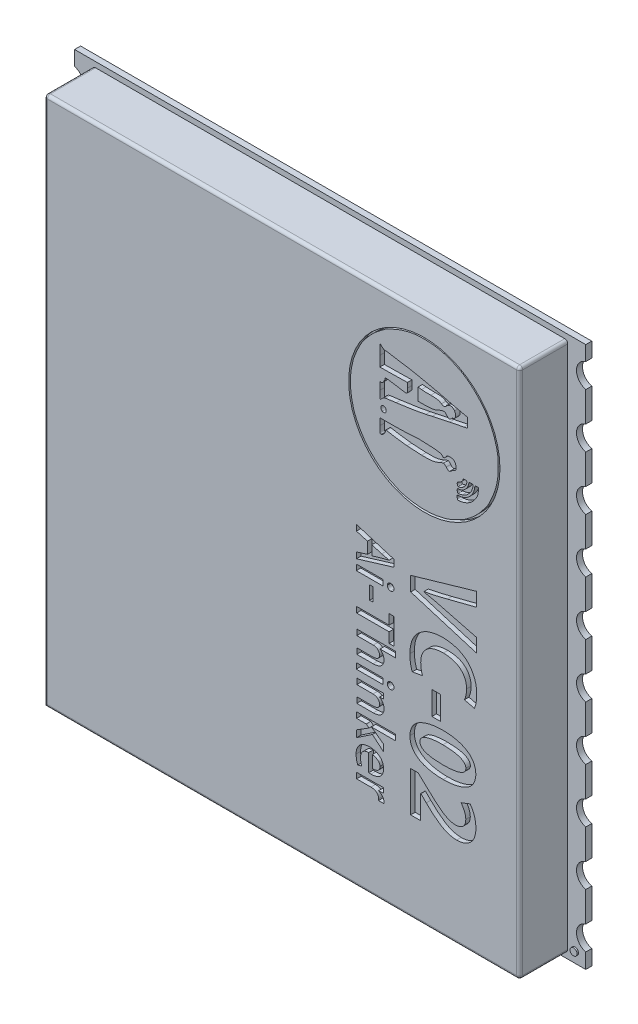
SolidWorks part; units mm, degrees
material "Alliage 1060"
ref_plane "Plan de face" through (0, 0, 0) normal (0, 0, 1) x (1, 0, 0)
ref_plane "Plan de dessus" through (0, 0, 0) normal (0, 1, 0) x (1, 0, 0)
ref_plane "Plan de droite" through (0, 0, 0) normal (1, 0, 0) x (0, 0, -1)
sketch "Esquisse1" plane through (0, 0, 0) normal (0, 0, 1) x (1, 0, 0)
  line L0 (-8.5, 9) -> (-8.5, 8.51) construction
  line L1 (-8.5, -9) -> (8.5, -9)
  line L2 (-8.5, -9) -> (-8.5, -8.4958)
  line L3 (-8.5, 9) -> (8.5, 9)
  line L4 (8.5, -9) -> (8.5, -8.4958)
  line L5 (-8.5, -9) -> (8.5, 9) construction
  line L6 (-8.5, 9) -> (8.5, -9) construction
  line L7 (-8.1924, 8.1048) -> (-8.0028, 8.1048) construction
  line L8 (-8.0028, 8.1048) -> (-8.0028, 8.6053) construction
  line L9 (-8.0028, 8.1048) -> (-8.0028, 7.6017) construction
  line L10 (-8.5, 8.6053) -> (-8.5, 8.51) construction
  line L11 (-8.5, 7.6044) -> (-8.0028, 7.6044)
  line L13 (-8.5, 8.6053) -> (-8.0028, 8.6053)
  line L14 (-8.0028, 7.6044) -> (-8.0028, 8.6053)
  line L15 (-8.2646, 8.3418) -> (-8.0028, 8.6053) construction
  line L16 (-8.2664, 7.8697) -> (-8.0028, 7.6044) construction
  line L17 (-8.5, 7.6044) -> (-8.5, 7.7042) construction
  line L18 (-8.5, 8.51) -> (-8.5, 9)
  line L19 (0, 9) -> (0, -9) construction
  line L20 (8.5, 7.6044) -> (8.0028, 7.6044)
  line L21 (8.0028, 7.6044) -> (8.0028, 8.6053)
  line L22 (8.5, 8.6053) -> (8.0028, 8.6053)
  line L23 (-8.5, 6.8053) -> (-8.0028, 6.8053)
  line L24 (-8.0028, 5.8044) -> (-8.0028, 6.8053)
  line L25 (-8.5, 5.8044) -> (-8.0028, 5.8044)
  line L26 (8.0028, 5.8044) -> (8.0028, 6.8053)
  line L27 (8.5, 6.8053) -> (8.0028, 6.8053)
  line L28 (8.5, 5.8044) -> (8.0028, 5.8044)
  line L29 (-8.5, 5.0053) -> (-8.0028, 5.0053)
  line L30 (-8.0028, 4.0044) -> (-8.0028, 5.0053)
  line L31 (-8.5, 4.0044) -> (-8.0028, 4.0044)
  line L32 (8.0028, 4.0044) -> (8.0028, 5.0053)
  line L33 (8.5, 5.0053) -> (8.0028, 5.0053)
  line L34 (8.5, 4.0044) -> (8.0028, 4.0044)
  line L35 (-8.5, 3.2053) -> (-8.0028, 3.2053)
  line L36 (-8.0028, 2.2044) -> (-8.0028, 3.2053)
  line L37 (-8.5, 2.2044) -> (-8.0028, 2.2044)
  line L38 (8.0028, 2.2044) -> (8.0028, 3.2053)
  line L39 (8.5, 3.2053) -> (8.0028, 3.2053)
  line L40 (8.5, 2.2044) -> (8.0028, 2.2044)
  line L41 (-8.5, 1.4053) -> (-8.0028, 1.4053)
  line L42 (-8.0028, 0.4044) -> (-8.0028, 1.4053)
  line L43 (-8.5, 0.4044) -> (-8.0028, 0.4044)
  line L44 (8.0028, 0.4044) -> (8.0028, 1.4053)
  line L45 (8.5, 1.4053) -> (8.0028, 1.4053)
  line L46 (8.5, 0.4044) -> (8.0028, 0.4044)
  line L47 (-8.5, -0.3947) -> (-8.0028, -0.3947)
  line L48 (-8.0028, -1.3956) -> (-8.0028, -0.3947)
  line L49 (-8.5, -1.3956) -> (-8.0028, -1.3956)
  line L50 (8.0028, -1.3956) -> (8.0028, -0.3947)
  line L51 (8.5, -0.3947) -> (8.0028, -0.3947)
  line L52 (8.5, -1.3956) -> (8.0028, -1.3956)
  line L53 (-8.5, -2.1947) -> (-8.0028, -2.1947)
  line L54 (-8.0028, -3.1956) -> (-8.0028, -2.1947)
  line L55 (-8.5, -3.1956) -> (-8.0028, -3.1956)
  line L56 (8.0028, -3.1956) -> (8.0028, -2.1947)
  line L57 (8.5, -2.1947) -> (8.0028, -2.1947)
  line L58 (8.5, -3.1956) -> (8.0028, -3.1956)
  line L59 (-8.5, -3.9947) -> (-8.0028, -3.9947)
  line L60 (-8.0028, -4.9956) -> (-8.0028, -3.9947)
  line L61 (-8.5, -4.9956) -> (-8.0028, -4.9956)
  line L62 (8.0028, -4.9956) -> (8.0028, -3.9947)
  line L63 (8.5, -3.9947) -> (8.0028, -3.9947)
  line L64 (8.5, -4.9956) -> (8.0028, -4.9956)
  line L65 (-8.5, -5.7947) -> (-8.0028, -5.7947)
  line L66 (-8.0028, -6.7956) -> (-8.0028, -5.7947)
  line L67 (-8.5, -6.7956) -> (-8.0028, -6.7956)
  line L68 (8.0028, -6.7956) -> (8.0028, -5.7947)
  line L69 (8.5, -5.7947) -> (8.0028, -5.7947)
  line L70 (8.5, -6.7956) -> (8.0028, -6.7956)
  line L71 (-8.5, -7.5947) -> (-8.0028, -7.5947)
  line L72 (-8.0028, -8.5956) -> (-8.0028, -7.5947)
  line L73 (-8.5, -8.5956) -> (-8.0028, -8.5956)
  line L74 (8.0028, -8.5956) -> (8.0028, -7.5947)
  line L75 (8.5, -7.5947) -> (8.0028, -7.5947)
  line L76 (8.5, -8.5956) -> (8.0028, -8.5956)
  line L77 (-8.5, 6.71) -> (-8.5, 7.7042)
  line L78 (-8.5, 4.91) -> (-8.5, 5.9042)
  line L79 (-8.5, 3.11) -> (-8.5, 4.1042)
  line L80 (-8.5, 1.31) -> (-8.5, 2.3042)
  line L81 (-8.5, -0.49) -> (-8.5, 0.5042)
  line L82 (-8.5, -2.29) -> (-8.5, -1.2958)
  line L83 (-8.5, -4.09) -> (-8.5, -3.0958)
  line L84 (-8.5, -5.89) -> (-8.5, -4.8958)
  line L85 (-8.5, -7.69) -> (-8.5, -6.6958)
  line L86 (8.5, 8.51) -> (8.5, 9)
  line L87 (8.5, 6.71) -> (8.5, 7.7042)
  line L88 (8.5, 3.11) -> (8.5, 5.9042)
  line L89 (8.5, -0.49) -> (8.5, 2.3042)
  line L90 (8.5, -2.29) -> (8.5, -1.2958)
  line L91 (8.5, -4.09) -> (8.5, -3.0958)
  line L92 (8.5, -5.89) -> (8.5, -4.8958)
  line L93 (8.5, -7.69) -> (8.5, -6.6958)
  arc A0 (-8.5, 8.51) -> (-8.5, 7.7042) centre (-8.61, 8.1071) cw
  arc A1 (8.5, 8.51) -> (8.5, 7.7042) centre (8.61, 8.1071) ccw
  arc A2 (-8.5, 6.71) -> (-8.5, 5.9042) centre (-8.61, 6.3071) cw
  arc A3 (8.5, 6.71) -> (8.5, 5.9042) centre (8.61, 6.3071) ccw
  arc A4 (-8.5, 4.91) -> (-8.5, 4.1042) centre (-8.61, 4.5071) cw
  arc A5 (8.5, 4.91) -> (8.5, 4.1042) centre (8.61, 4.5071) ccw
  arc A6 (-8.5, 3.11) -> (-8.5, 2.3042) centre (-8.61, 2.7071) cw
  arc A7 (8.5, 3.11) -> (8.5, 2.3042) centre (8.61, 2.7071) ccw
  arc A8 (-8.5, 1.31) -> (-8.5, 0.5042) centre (-8.61, 0.9071) cw
  arc A9 (8.5, 1.31) -> (8.5, 0.5042) centre (8.61, 0.9071) ccw
  arc A10 (-8.5, -0.49) -> (-8.5, -1.2958) centre (-8.61, -0.8929) cw
  arc A11 (8.5, -0.49) -> (8.5, -1.2958) centre (8.61, -0.8929) ccw
  arc A12 (-8.5, -2.29) -> (-8.5, -3.0958) centre (-8.61, -2.6929) cw
  arc A13 (8.5, -2.29) -> (8.5, -3.0958) centre (8.61, -2.6929) ccw
  arc A14 (-8.5, -4.09) -> (-8.5, -4.8958) centre (-8.61, -4.4929) cw
  arc A15 (8.5, -4.09) -> (8.5, -4.8958) centre (8.61, -4.4929) ccw
  arc A16 (-8.5, -5.89) -> (-8.5, -6.6958) centre (-8.61, -6.2929) cw
  arc A17 (8.5, -5.89) -> (8.5, -6.6958) centre (8.61, -6.2929) ccw
  arc A18 (-8.5, -7.69) -> (-8.5, -8.4958) centre (-8.61, -8.0929) cw
  arc A19 (8.5, -7.69) -> (8.5, -8.4958) centre (8.61, -8.0929) ccw
  point P0 (0, 0)
  dimension "D1" = 17
  dimension "D2" = 18
  dimension "D3" = 10
extrude "Boss.-Extru.1" add sketch "Esquisse1" along normal blind 0.2 contours L75 L93 L70 L68 L69 L92 L64 L62 L63 L91 L58 L56 L57 L90 L52 L50 L51 L89 L46 L44 L45 L40 L38 L39 L88 L34 L32 L33 L28 L26 L27 L87 L20 L21 L22 L86 L3 L18 L13 L14 L11 L77 L23 L24 L25 L78 L29 L30 L31 | L18 A0 L77 L11 L14 L13 | L77 A2 L78 L25 L24 L23 | L78 A4 L79 L31 L30 L29 | L79 A6 L80 L37 L36 L35 | L80 A8 L81 L43 L42 L41 | L81 A10 L82 L49 L48 L47 | L82 A12 L83 L55 L54 L53 | L83 A14 L84 L61 L60 L59 | L84 A16 L85 L67 L66 L65 | L85 A18 L2 L73 L72 L71 | A1 L86 L22 L21 L20 L87 | A3 L87 L27 L26 L28 L88 | A5 L88 L33 L32 L34 | A7 L88 L39 L38 L40 L89 | A9 L89 L45 L44 L46 | A11 L89 L51 L50 L52 L90 | A13 L90 L57 L56 L58 L91 | A15 L91 L63 L62 L64 L92 | A17 L92 L69 L68 L70 L93 | A19 L93 L75 L74 L76 L4 region at (0, -0.0002, 0) region at (-8.1811, -8.0965, 0) region at (8.1811, -8.0965, 0) region at (-8.1811, -6.2965, 0) region at (8.1811, -6.2965, 0) region at (-8.1811, -4.4965, 0) region at (8.1811, -4.4965, 0) region at (-8.1811, -2.6965, 0) region at (8.1811, -2.6965, 0) region at (-8.1811, -0.8965, 0) region at (8.1811, -0.8965, 0) region at (-8.1811, 0.9035, 0) region at (8.1811, 0.9035, 0) region at (-8.1811, 2.7035, 0) region at (8.1811, 2.7035, 0) region at (-8.1811, 4.5035, 0) region at (8.1811, 4.5035, 0) region at (-8.1811, 6.3035, 0) region at (8.1811, 6.3035, 0) region at (-8.1811, 8.1035, 0) region at (8.1811, 8.1035, 0)
sketch "Esquisse2" plane through (0, 0, 0.2) normal (0, 0, 1) x (1, 0, 0)
  line L1 (-7.9016, -8.8212) -> (7.9016, -8.8212)
  line L2 (-7.9016, -8.8212) -> (-7.9016, 8.8212)
  line L3 (-7.9016, 8.8212) -> (7.9016, 8.8212)
  line L4 (7.9016, -8.8212) -> (7.9016, 8.8212)
  line L5 (-7.9016, -8.8212) -> (7.9016, 8.8212) construction
  line L6 (-7.9016, 8.8212) -> (7.9016, -8.8212) construction
  point P0 (0, 0)
extrude "Boss.-Extru.2" add sketch "Esquisse2" along normal blind 1.6
fillet "Congé1" radius 0.1 7 edges at (7.9016, -8.8212, 1) (-7.9016, 8.8212, 1) (7.9016, 8.8212, 1) (0, 8.8212, 1.8) (7.9016, 0, 1.8) (0, -8.8212, 1.8) (-7.9016, 0, 1.8)
sketch "Esquisse3" plane through (0, 0, 0.2) normal (0, 0, 1) x (1, 0, 0)
  circle A0 centre (8.1429, -8.6444) radius 0.1165
extrude "Boss.-Extru.3" add sketch "Esquisse3" along normal blind 0.05
sketch "Esquisse4" plane through (4.0778, 3.5696, 1.8) normal (0, 0, 1) x (0, -1, 0)
  line L0 (-2.9667, -0.368) -> (-2.9744, 0.0906)
  line L1 (-2.9744, 0.0906) -> (-2.8102, 0.0906)
  line L2 (-2.5452, -0.7857) -> (-2.553, -0.8265)
  line L3 (-2.553, -0.8265) -> (-2.2899, -0.8265)
  line L4 (-2.6311, 1.9732) -> (-2.6513, 2.0834)
  line L5 (-2.6513, 2.0834) -> (-2.8119, 2.0834)
  line L6 (-2.8119, 2.0834) -> (-2.9724, 2.0834)
  line L7 (-2.9724, 2.0834) -> (-3.0142, 1.8938)
  line L8 (-3.2964, -0.8265) -> (-2.9591, -0.8265)
  line L9 (-2.9591, -0.8265) -> (-2.9667, -0.368)
  line L10 (-2.6108, 0.6535) -> (-2.6108, 0.4433)
  line L11 (-2.6108, 0.4433) -> (-2.8151, 0.4433)
  line L12 (-2.8151, 0.4433) -> (-3.0193, 0.4433)
  line L13 (-3.0193, 0.4433) -> (-3.0053, 0.5623)
  line L14 (-1.5006, -0.4076) -> (-1.4998, -0.8265)
  line L15 (-1.4998, -0.8265) -> (-1.2705, -0.8265)
  line L16 (-1.0074, 2.4486) -> (-1.1295, 2.4588)
  line L17 (-1.1295, 2.4588) -> (-1.1295, 2.397)
  line L18 (-0.5699, 1.8409) -> (-0.5602, 1.7483)
  line L19 (-0.5602, 1.7483) -> (-0.4921, 1.7483)
  line L20 (-2.0465, 3.1105) -> (-2.0192, -1.8037) construction
  line L21 (-4.5021, 0.6549) -> (0.4101, 0.7018) construction
  circle A0 centre (-2.0329, 0.6534) radius 2.516
  spline S0 degree 3 poles (-2.267, -1.795) (-2.4108, -1.7826) (-2.4888, -1.7682) (-2.7343, -1.7088) knots 0 0 0 0 1 1 1 1
  spline S1 degree 3 poles (-2.7343, -1.7088) (-2.8848, -1.6724) (-3.28, -1.4898) (-3.3951, -1.4036) knots 0 0 0 0 1 1 1 1
  spline S2 degree 3 poles (-3.3951, -1.4036) (-3.4239, -1.382) (-3.4993, -1.3255) (-3.5626, -1.2781) knots 0 0 0 0 1 1 1 1
  spline S3 degree 3 poles (-3.5626, -1.2781) (-3.7172, -1.1624) (-3.8836, -0.9907) (-4.0177, -0.8088) knots 0 0 0 0 1 1 1 1
  spline S4 degree 3 poles (-4.0177, -0.8088) (-4.0784, -0.7264) (-4.1353, -0.6501) (-4.1439, -0.6393) knots 0 0 0 0 1 1 1 1
  spline S5 degree 3 poles (-4.1439, -0.6393) (-4.1756, -0.5998) (-4.3364, -0.2503) (-4.3702, -0.1475) knots 0 0 0 0 1 1 1 1
  spline S6 degree 3 poles (-4.3702, -0.1475) (-4.477, 0.1775) (-4.5021, 0.3305) (-4.5021, 0.6549) knots 0 0 0 0 1 1 1 1
  spline S7 degree 3 poles (-4.5021, 0.6549) (-4.5021, 0.9793) (-4.477, 1.1323) (-4.3702, 1.4573) knots 0 0 0 0 1 1 1 1
  spline S8 degree 3 poles (-4.3702, 1.4573) (-4.3286, 1.5839) (-4.169, 1.9209) (-4.1343, 1.9557) knots 0 0 0 0 1 1 1 1
  spline S9 degree 3 poles (-4.1343, 1.9557) (-4.1207, 1.9692) (-4.1005, 1.9975) (-4.0894, 2.0186) knots 0 0 0 0 1 1 1 1
  spline S10 degree 3 poles (-4.0894, 2.0186) (-3.9946, 2.1985) (-3.5901, 2.603) (-3.4102, 2.6978) knots 0 0 0 0 1 1 1 1
  spline S11 degree 3 poles (-3.4102, 2.6978) (-3.3892, 2.7089) (-3.3608, 2.7291) (-3.3473, 2.7427) knots 0 0 0 0 1 1 1 1
  spline S12 degree 3 poles (-3.3473, 2.7427) (-3.3125, 2.7774) (-2.9755, 2.937) (-2.8489, 2.9786) knots 0 0 0 0 1 1 1 1
  spline S13 degree 3 poles (-2.8489, 2.9786) (-2.5239, 3.0854) (-2.3709, 3.1105) (-2.0465, 3.1105) knots 0 0 0 0 1 1 1 1
  spline S14 degree 3 poles (-2.0465, 3.1105) (-1.7221, 3.1105) (-1.5691, 3.0854) (-1.2441, 2.9786) knots 0 0 0 0 1 1 1 1
  spline S15 degree 3 poles (-1.2441, 2.9786) (-1.1413, 2.9448) (-0.7918, 2.784) (-0.7523, 2.7523) knots 0 0 0 0 1 1 1 1
  spline S16 degree 3 poles (-0.7523, 2.7523) (-0.7415, 2.7436) (-0.6652, 2.6868) (-0.5828, 2.6261) knots 0 0 0 0 1 1 1 1
  spline S17 degree 3 poles (-0.5828, 2.6261) (-0.4009, 2.492) (-0.2292, 2.3255) (-0.1135, 2.171) knots 0 0 0 0 1 1 1 1
  spline S18 degree 3 poles (-0.1135, 2.171) (-0.0661, 2.1077) (-0.0096, 2.0323) (0.012, 2.0035) knots 0 0 0 0 1 1 1 1
  spline S19 degree 3 poles (0.012, 2.0035) (0.0982, 1.8883) (0.2807, 1.4932) (0.3172, 1.3427) knots 0 0 0 0 1 1 1 1
  spline S20 degree 3 poles (0.3172, 1.3427) (0.375, 1.1039) (0.3902, 1.0167) (0.404, 0.8445) knots 0 0 0 0 1 1 1 1
  spline S21 degree 3 poles (0.404, 0.8445) (0.4302, 0.5163) (0.371, 0.064) (0.2695, -0.1828) knots 0 0 0 0 1 1 1 1
  spline S22 degree 3 poles (0.2695, -0.1828) (0.0616, -0.6881) (-0.2009, -1.0347) (-0.6004, -1.3318) knots 0 0 0 0 1 1 1 1
  spline S23 degree 3 poles (-0.6004, -1.3318) (-0.7952, -1.4766) (-1.173, -1.6679) (-1.326, -1.6991) knots 0 0 0 0 1 1 1 1
  spline S24 degree 3 poles (-1.326, -1.6991) (-1.3586, -1.7057) (-1.409, -1.7181) (-1.4381, -1.7265) knots 0 0 0 0 1 1 1 1
  spline S25 degree 3 poles (-1.4381, -1.7265) (-1.6677, -1.7931) (-1.9844, -1.8193) (-2.267, -1.795) knots 0 0 0 0 1 1 1 1
  spline S26 degree 3 poles (-2.8102, 0.0906) (-2.6221, 0.0906) (-2.6304, 0.1011) (-2.665, -0.0946) knots 0 0 0 0 1 1 1 1
  spline S27 degree 3 poles (-2.665, -0.0946) (-2.6753, -0.1528) (-2.6911, -0.252) (-2.7002, -0.3151) knots 0 0 0 0 1 1 1 1
  spline S28 degree 3 poles (-2.7002, -0.3151) (-2.7093, -0.3781) (-2.7236, -0.4733) (-2.7321, -0.5267) knots 0 0 0 0 1 1 1 1
  spline S29 degree 3 poles (-2.7321, -0.5267) (-2.7489, -0.6326) (-2.7453, -0.6501) (-2.7064, -0.6501) knots 0 0 0 0 1 1 1 1
  spline S30 degree 3 poles (-2.7064, -0.6501) (-2.6922, -0.6501) (-2.6484, -0.6714) (-2.609, -0.6975) knots 0 0 0 0 1 1 1 1
  spline S31 degree 3 poles (-2.609, -0.6975) (-2.5525, -0.7349) (-2.5391, -0.7534) (-2.5452, -0.7857) knots 0 0 0 0 1 1 1 1
  spline S32 degree 3 poles (-2.2899, -0.8265) (-2.0082, -0.8265) (-2.0041, -0.8247) (-2.1012, -0.7429) knots 0 0 0 0 1 1 1 1
  spline S33 degree 3 poles (-2.1012, -0.7429) (-2.132, -0.717) (-2.1517, -0.6798) (-2.1574, -0.6369) knots 0 0 0 0 1 1 1 1
  spline S34 degree 3 poles (-2.1574, -0.6369) (-2.1622, -0.6005) (-2.1833, -0.4398) (-2.2043, -0.2798) knots 0 0 0 0 1 1 1 1
  spline S35 degree 3 poles (-2.2043, -0.2798) (-2.2636, 0.1717) (-2.3254, 0.5547) (-2.3637, 0.7078) knots 0 0 0 0 1 1 1 1
  spline S36 degree 3 poles (-2.3637, 0.7078) (-2.3722, 0.7418) (-2.3923, 0.833) (-2.4084, 0.9106) knots 0 0 0 0 1 1 1 1
  spline S37 degree 3 poles (-2.4084, 0.9106) (-2.438, 1.0536) (-2.4838, 1.268) (-2.5326, 1.4926) knots 0 0 0 0 1 1 1 1
  spline S38 degree 3 poles (-2.5326, 1.4926) (-2.577, 1.6969) (-2.6098, 1.8568) (-2.6311, 1.9732) knots 0 0 0 0 1 1 1 1
  spline S39 degree 3 poles (-3.0142, 1.8938) (-3.0373, 1.7895) (-3.0626, 1.6804) (-3.0704, 1.6513) knots 0 0 0 0 1 1 1 1
  spline S40 degree 3 poles (-3.0704, 1.6513) (-3.114, 1.4904) (-3.1649, 1.2846) (-3.186, 1.184) knots 0 0 0 0 1 1 1 1
  spline S41 degree 3 poles (-3.186, 1.184) (-3.1992, 1.1209) (-3.2224, 1.0177) (-3.2376, 0.9547) knots 0 0 0 0 1 1 1 1
  spline S42 degree 3 poles (-3.2376, 0.9547) (-3.2527, 0.8917) (-3.2765, 0.7845) (-3.2903, 0.7166) knots 0 0 0 0 1 1 1 1
  spline S43 degree 3 poles (-3.2903, 0.7166) (-3.3042, 0.6487) (-3.3281, 0.5337) (-3.3435, 0.4609) knots 0 0 0 0 1 1 1 1
  spline S44 degree 3 poles (-3.3435, 0.4609) (-3.3917, 0.2334) (-3.406, 0.1513) (-3.459, -0.2004) knots 0 0 0 0 1 1 1 1
  spline S45 degree 3 poles (-3.459, -0.2004) (-3.478, -0.3265) (-3.5012, -0.468) (-3.5107, -0.5148) knots 0 0 0 0 1 1 1 1
  spline S46 degree 3 poles (-3.5107, -0.5148) (-3.5202, -0.5616) (-3.5279, -0.6239) (-3.5279, -0.6532) knots 0 0 0 0 1 1 1 1
  spline S47 degree 3 poles (-3.5279, -0.6532) (-3.5279, -0.6897) (-3.5446, -0.7221) (-3.5808, -0.7559) knots 0 0 0 0 1 1 1 1
  spline S48 degree 3 poles (-3.5808, -0.7559) (-3.6099, -0.7831) (-3.6337, -0.8101) (-3.6337, -0.8159) knots 0 0 0 0 1 1 1 1
  spline S49 degree 3 poles (-3.6337, -0.8159) (-3.6337, -0.8217) (-3.4819, -0.8265) (-3.2964, -0.8265) knots 0 0 0 0 1 1 1 1
  spline S50 degree 3 poles (-3.0053, 0.5623) (-2.9976, 0.6278) (-2.9928, 0.7647) (-2.9947, 0.8665) knots 0 0 0 0 1 1 1 1
  spline S51 degree 3 poles (-2.9947, 0.8665) (-2.9983, 1.0582) (-2.9821, 1.1418) (-2.9258, 1.222) knots 0 0 0 0 1 1 1 1
  spline S52 degree 3 poles (-2.9258, 1.222) (-2.8783, 1.2897) (-2.885, 1.3312) (-2.9547, 1.4009) knots 0 0 0 0 1 1 1 1
  spline S53 degree 3 poles (-2.9547, 1.4009) (-3.0438, 1.49) (-3.0366, 1.5987) (-2.9374, 1.6599) knots 0 0 0 0 1 1 1 1
  spline S54 degree 3 poles (-2.9374, 1.6599) (-2.834, 1.7238) (-2.699, 1.6918) (-2.699, 1.6033) knots 0 0 0 0 1 1 1 1
  spline S55 degree 3 poles (-2.699, 1.6033) (-2.699, 1.5881) (-2.687, 1.5711) (-2.6724, 1.5655) knots 0 0 0 0 1 1 1 1
  spline S56 degree 3 poles (-2.6724, 1.5655) (-2.6578, 1.5599) (-2.6367, 1.5354) (-2.6256, 1.511) knots 0 0 0 0 1 1 1 1
  spline S57 degree 3 poles (-2.6256, 1.511) (-2.6072, 1.4705) (-2.6118, 1.4613) (-2.6804, 1.4011) knots 0 0 0 0 1 1 1 1
  spline S58 degree 3 poles (-2.6804, 1.4011) (-2.7499, 1.3402) (-2.7545, 1.3307) (-2.7446, 1.2688) knots 0 0 0 0 1 1 1 1
  spline S59 degree 3 poles (-2.7446, 1.2688) (-2.7388, 1.2321) (-2.7189, 1.1752) (-2.7005, 1.1425) knots 0 0 0 0 1 1 1 1
  spline S60 degree 3 poles (-2.7005, 1.1425) (-2.64, 1.0347) (-2.6108, 0.8758) (-2.6108, 0.6535) knots 0 0 0 0 1 1 1 1
  spline S61 degree 3 poles (-1.0413, -0.7856) (-1.0413, -0.7304) (-1.1607, -0.6325) (-1.2281, -0.6325) knots 0 0 0 0 1 1 1 1
  spline S62 degree 3 poles (-1.2281, -0.6325) (-1.248, -0.6325) (-1.2531, -0.6232) (-1.245, -0.6019) knots 0 0 0 0 1 1 1 1
  spline S63 degree 3 poles (-1.245, -0.6019) (-1.2273, -0.5559) (-1.1669, -0.1477) (-1.1444, 0.0773) knots 0 0 0 0 1 1 1 1
  spline S64 degree 3 poles (-1.1444, 0.0773) (-1.1335, 0.1864) (-1.1212, 0.4052) (-1.117, 0.5634) knots 0 0 0 0 1 1 1 1
  spline S65 degree 3 poles (-1.117, 0.5634) (-1.1088, 0.8762) (-1.1251, 0.9841) (-1.2095, 1.1749) knots 0 0 0 0 1 1 1 1
  spline S66 degree 3 poles (-1.2095, 1.1749) (-1.2334, 1.2289) (-1.2529, 1.2839) (-1.2529, 1.297) knots 0 0 0 0 1 1 1 1
  spline S67 degree 3 poles (-1.2529, 1.297) (-1.2529, 1.3101) (-1.2212, 1.3486) (-1.1824, 1.3826) knots 0 0 0 0 1 1 1 1
  spline S68 degree 3 poles (-1.1824, 1.3826) (-1.1027, 1.4524) (-1.0957, 1.4857) (-1.1485, 1.5418) knots 0 0 0 0 1 1 1 1
  spline S69 degree 3 poles (-1.1485, 1.5418) (-1.1686, 1.5632) (-1.1957, 1.6058) (-1.2086, 1.6364) knots 0 0 0 0 1 1 1 1
  spline S70 degree 3 poles (-1.2086, 1.6364) (-1.2359, 1.7012) (-1.2816, 1.7202) (-1.3727, 1.7047) knots 0 0 0 0 1 1 1 1
  spline S71 degree 3 poles (-1.3727, 1.7047) (-1.4705, 1.6881) (-1.5183, 1.6437) (-1.5297, 1.5588) knots 0 0 0 0 1 1 1 1
  spline S72 degree 3 poles (-1.5297, 1.5588) (-1.5435, 1.4558) (-1.5253, 1.4022) (-1.4644, 1.3663) knots 0 0 0 0 1 1 1 1
  spline S73 degree 3 poles (-1.4644, 1.3663) (-1.4123, 1.3354) (-1.3949, 1.2845) (-1.4294, 1.2632) knots 0 0 0 0 1 1 1 1
  spline S74 degree 3 poles (-1.4294, 1.2632) (-1.4881, 1.227) (-1.5079, 1.1352) (-1.5225, 0.8313) knots 0 0 0 0 1 1 1 1
  spline S75 degree 3 poles (-1.5225, 0.8313) (-1.5423, 0.4185) (-1.5423, 0.4092) (-1.5204, 0.1964) knots 0 0 0 0 1 1 1 1
  spline S76 degree 3 poles (-1.5204, 0.1964) (-1.5099, 0.0945) (-1.501, -0.1773) (-1.5006, -0.4076) knots 0 0 0 0 1 1 1 1
  spline S77 degree 3 poles (-1.2705, -0.8265) (-1.0425, -0.8265) (-1.0413, -0.8263) (-1.0413, -0.7856) knots 0 0 0 0 1 1 1 1
  spline S78 degree 3 poles (-1.7259, -0.7471) (-1.6953, -0.68) (-1.7308, -0.6149) (-1.798, -0.6149) knots 0 0 0 0 1 1 1 1
  spline S79 degree 3 poles (-1.798, -0.6149) (-1.8861, -0.6149) (-1.9278, -0.6812) (-1.8872, -0.7571) knots 0 0 0 0 1 1 1 1
  spline S80 degree 3 poles (-1.8872, -0.7571) (-1.8585, -0.8106) (-1.7518, -0.804) (-1.7259, -0.7471) knots 0 0 0 0 1 1 1 1
  spline S81 degree 3 poles (-0.8173, 1.7777) (-0.8108, 1.7945) (-0.8264, 1.8459) (-0.8538, 1.8982) knots 0 0 0 0 1 1 1 1
  spline S82 degree 3 poles (-0.8538, 1.8982) (-0.9052, 1.9964) (-1.0002, 2.0657) (-1.0834, 2.0657) knots 0 0 0 0 1 1 1 1
  spline S83 degree 3 poles (-1.0834, 2.0657) (-1.1243, 2.0657) (-1.1295, 2.0588) (-1.1295, 2.004) knots 0 0 0 0 1 1 1 1
  spline S84 degree 3 poles (-1.1295, 2.004) (-1.1295, 1.9592) (-1.1217, 1.9423) (-1.1012, 1.9423) knots 0 0 0 0 1 1 1 1
  spline S85 degree 3 poles (-1.1012, 1.9423) (-1.0603, 1.9423) (-0.9531, 1.8288) (-0.9531, 1.7853) knots 0 0 0 0 1 1 1 1
  spline S86 degree 3 poles (-0.9531, 1.7853) (-0.9531, 1.7547) (-0.9423, 1.7483) (-0.8908, 1.7483) knots 0 0 0 0 1 1 1 1
  spline S87 degree 3 poles (-0.8908, 1.7483) (-0.849, 1.7483) (-0.8249, 1.7579) (-0.8173, 1.7777) knots 0 0 0 0 1 1 1 1
  spline S88 degree 3 poles (-0.618, 1.778) (-0.618, 1.7943) (-0.6315, 1.8558) (-0.6479, 1.9147) knots 0 0 0 0 1 1 1 1
  spline S89 degree 3 poles (-0.6479, 1.9147) (-0.6718, 2) (-0.6959, 2.0395) (-0.767, 2.1098) knots 0 0 0 0 1 1 1 1
  spline S90 degree 3 poles (-0.767, 2.1098) (-0.857, 2.1988) (-0.8926, 2.2207) (-1.0073, 2.2573) knots 0 0 0 0 1 1 1 1
  spline S91 degree 3 poles (-1.0073, 2.2573) (-1.1146, 2.2915) (-1.1295, 2.2856) (-1.1295, 2.2088) knots 0 0 0 0 1 1 1 1
  spline S92 degree 3 poles (-1.1295, 2.2088) (-1.1295, 2.1439) (-1.126, 2.1396) (-1.0656, 2.1282) knots 0 0 0 0 1 1 1 1
  spline S93 degree 3 poles (-1.0656, 2.1282) (-0.9067, 2.0984) (-0.7591, 1.9413) (-0.7591, 1.8019) knots 0 0 0 0 1 1 1 1
  spline S94 degree 3 poles (-0.7591, 1.8019) (-0.7591, 1.7511) (-0.7554, 1.7483) (-0.6886, 1.7483) knots 0 0 0 0 1 1 1 1
  spline S95 degree 3 poles (-0.6886, 1.7483) (-0.6342, 1.7483) (-0.618, 1.7551) (-0.618, 1.778) knots 0 0 0 0 1 1 1 1
  spline S96 degree 3 poles (-0.4242, 1.8056) (-0.4245, 1.8755) (-0.4616, 2.002) (-0.509, 2.0943) knots 0 0 0 0 1 1 1 1
  spline S97 degree 3 poles (-0.509, 2.0943) (-0.5642, 2.2017) (-0.6476, 2.2882) (-0.7713, 2.3663) knots 0 0 0 0 1 1 1 1
  spline S98 degree 3 poles (-0.7713, 2.3663) (-0.8673, 2.427) (-0.9045, 2.44) (-1.0074, 2.4486) knots 0 0 0 0 1 1 1 1
  spline S99 degree 3 poles (-1.1295, 2.397) (-1.1295, 2.3361) (-1.1282, 2.335) (-1.0425, 2.3249) knots 0 0 0 0 1 1 1 1
  spline S100 degree 3 poles (-1.0425, 2.3249) (-0.8073, 2.297) (-0.5948, 2.0794) (-0.5699, 1.8409) knots 0 0 0 0 1 1 1 1
  spline S101 degree 3 poles (-0.4921, 1.7483) (-0.427, 1.7483) (-0.4241, 1.7508) (-0.4242, 1.8056) knots 0 0 0 0 1 1 1 1
extrude "Enlèv. mat.-Extru.1" cut sketch "Esquisse4" against normal blind 0.15 contours S48 S49 L8 L9 L0 L1 S26 S27 S28 S29 S30 S31 L2 L3 S32 S33 S34 S35 S36 S37 S38 L4 L5 L6 L7 S39 S40 S41 S42 S43 S44 S45 S46 S47 S59 S60 L10 L11 L12 L13 S50 S51 S52 S53 S54 S55 S56 S57 S58 | L15 S77 S61 S62 S63 S64 S65 S66 S67 S68 S69 S70 S71 S72 S73 S74 S75 S76 L14 | S79 S80 S78 | S86 S87 S81 S82 S83 S84 S85 | S94 S95 S88 S89 S90 S91 S92 S93 | L19 S101 S96 S97 S98 L16 L17 S99 S100 L18 | A0 S24 S25 S0 S1 S2 S3 S4 S5 S6 S7 S8 S9 S10 S11 S12 S13 S14 S15 S16 S17 S18 S19 S20 S21 S22 S23 region at (4.3643, 6.4064, 1.8) region at (4.4993, 4.9003, 1.8) region at (6.236, 4.284, 1.8) region at (4.7313, 8.1114, 1.8) region at (3.3739, 5.3781, 1.8) region at (5.9918, 4.5365, 1.8) region at (6.1188, 4.4159, 1.8)
sketch "Esquisse5" plane through (6.2504, -0.9228, 1.8) normal (0, 0, 1) x (0, -1, 0)
  text T0 "VC-02" font "@Adobe Gothic Std B" height in points 7
extrude "Enlèv. mat.-Extru.2" cut sketch "Esquisse5" against normal blind 0.15
sketch "Esquisse6" plane through (4.5451, -1.9237, 1.8) normal (0, 0, 1) x (0, -1, 0)
  text T0 "Ai-Thinker" font "@Adobe Heiti Std R" height in points 4
extrude "Enlèv. mat.-Extru.3" cut sketch "Esquisse6" against normal blind 0.15
